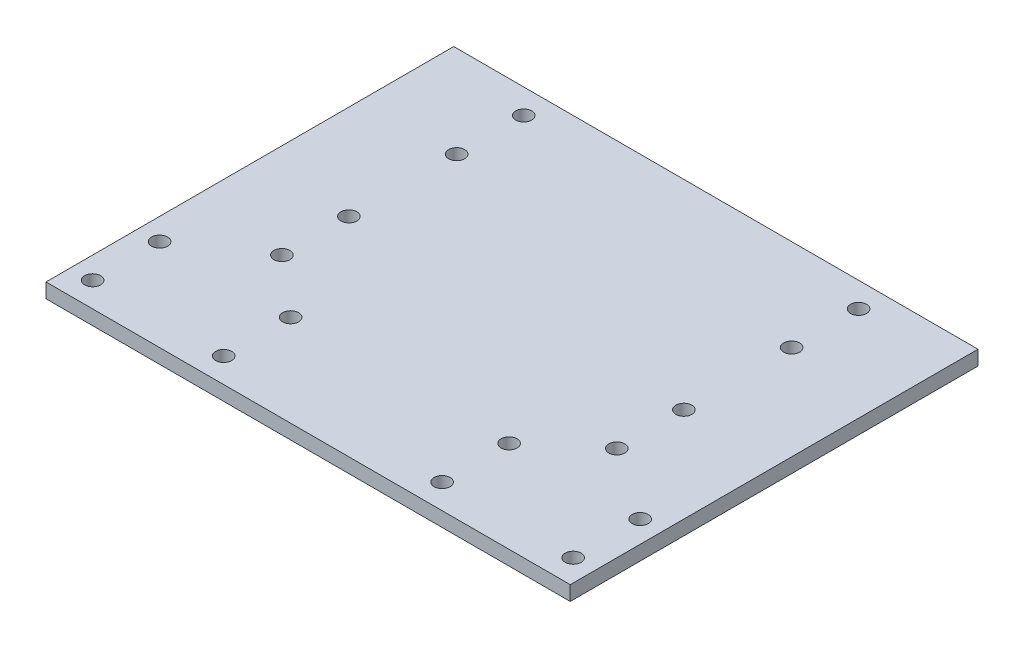
SolidWorks part; units mm, degrees
ref_plane "Front Plane" through (0, 0, 0) normal (0, 0, 1) x (1, 0, 0)
ref_plane "Top Plane" through (0, 0, 0) normal (0, 1, 0) x (1, 0, 0)
ref_plane "Right Plane" through (0, 0, 0) normal (1, 0, 0) x (0, 0, -1)
sketch "Sketch1" plane through (0, 0, 0) normal (0, 1, 0) x (1, 0, 0)
  line L1 (90, -70) -> (-90, -70)
  line L2 (90, -70) -> (90, 70)
  line L3 (90, 70) -> (-90, 70)
  line L4 (-90, -70) -> (-90, 70)
  line L5 (90, -70) -> (-90, 70) construction
  line L6 (90, 70) -> (-90, -70) construction
  point P0 (0, 0)
  dimension "D1" = 180
  dimension "D2" = 140
extrude "Body" add sketch "Sketch1" along normal blind 5
sketch "Sketch2" plane through (0, 5, 0) normal (0, 1, 0) x (1, 0, 0)
  line L0 (0, -1000) -> (0, 49000) construction
  circle A0 centre (-57.5, 61.5) radius 2.75
  circle A1 centre (-57.5, 38.5) radius 2.75
  circle A2 centre (-57.5, 1.5) radius 2.75
  circle A3 centre (-57.5, -21.5) radius 2.75
  circle A4 centre (-82.5, -38.5) radius 2.75
  circle A5 centre (-82.5, -61.5) radius 2.75
  circle A6 centre (-37.5, -61.5) radius 2.75
  circle A7 centre (-37.5, -38.5) radius 2.75
  circle A8 centre (37.5, -38.5) radius 2.75
  circle A9 centre (37.5, -61.5) radius 2.75
  circle A10 centre (82.5, -61.5) radius 2.75
  circle A11 centre (82.5, -38.5) radius 2.75
  circle A12 centre (57.5, -21.5) radius 2.75
  circle A13 centre (57.5, 1.5) radius 2.75
  circle A14 centre (57.5, 38.5) radius 2.75
  circle A15 centre (57.5, 61.5) radius 2.75
  dimension "D1" = 5.5
extrude "Holes" cut sketch "Sketch2" against normal through all
